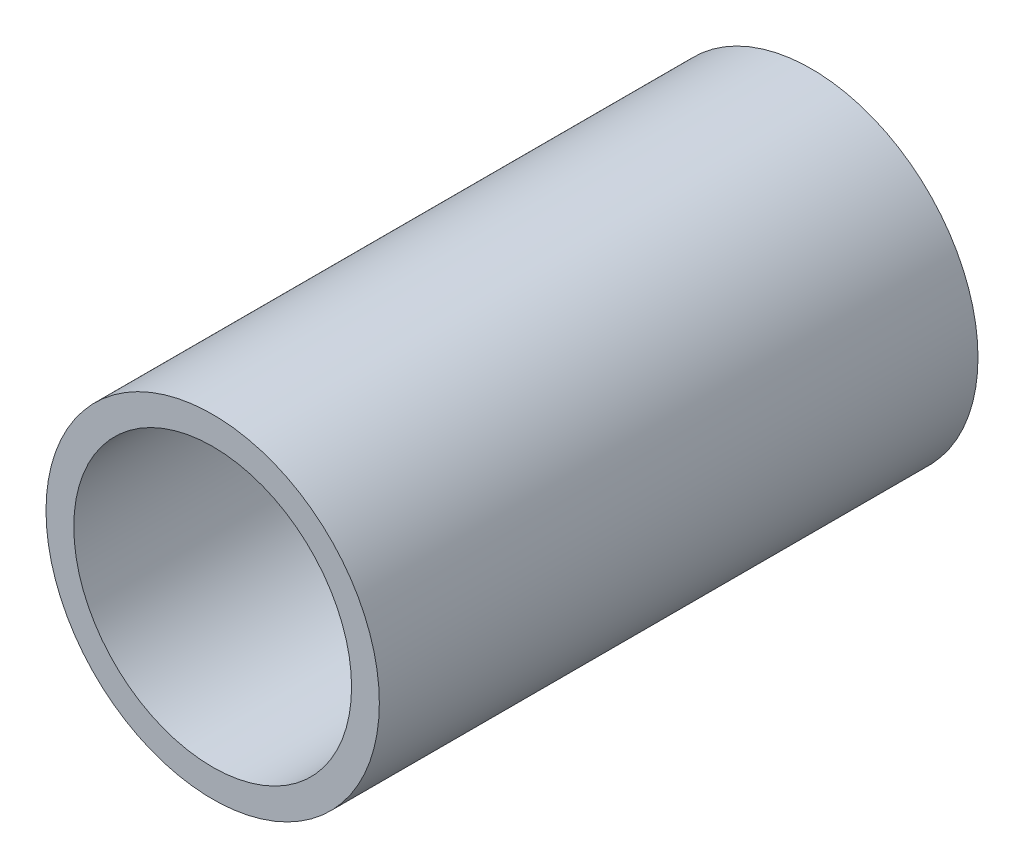
SolidWorks part; units mm, degrees
material "PLA 50%"
ref_plane "Front Plane" through (0, 0, 0) normal (0, 0, 1) x (1, 0, 0)
ref_plane "Top Plane" through (0, 0, 0) normal (0, 1, 0) x (1, 0, 0)
ref_plane "Right Plane" through (0, 0, 0) normal (1, 0, 0) x (0, 0, -1)
ref_axis "X" through (-88.99, 0, 0) along (1, 0, 0)
ref_axis "Y" through (0, 55, 0) along (0, -1, 0)
ref_axis "Z" through (0, 0, -88.99) along (0, 0, 1)
sketch "Sketch1" plane through (0, 0, 0) normal (0, 0, 1) x (1, 0, 0)
  circle A0 centre (0, 0) radius 5
  circle A1 centre (0, 0) radius 6
  dimension "D1" = 10
  dimension "D2" = 12
extrude "Boss-Extrude1" add sketch "Sketch1" against normal up to surface (21.5512 mm away)
